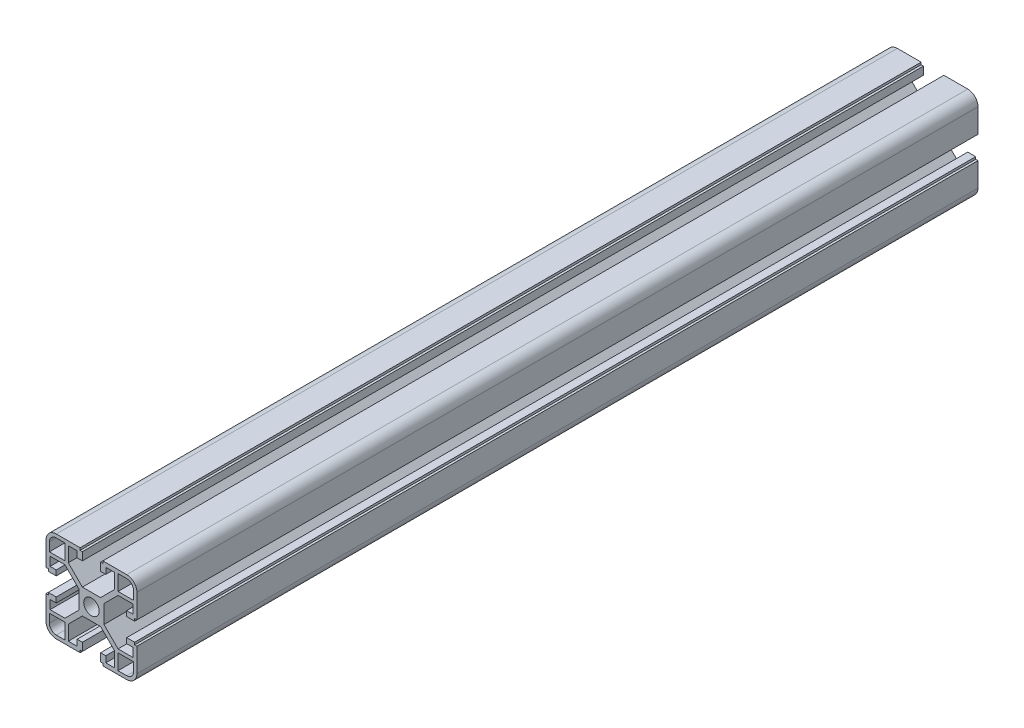
SolidWorks part; units mm, degrees
material "6061-T6 (SS)"
ref_plane "Front Plane" through (0, 0, 0) normal (0, 0, 1) x (1, 0, 0)
ref_plane "Top Plane" through (0, 0, 0) normal (0, 1, 0) x (1, 0, 0)
ref_plane "Right Plane" through (0, 0, 0) normal (1, 0, 0) x (0, 0, -1)
sketch "Sketch1" plane through (0, 0, 0) normal (0, 0, 1) x (1, 0, 0)
  line L0 (3.4, 0) -> (5.5, 0)
  line L1 (10.19, 11.69) -> (4, 5.5)
  line L2 (11.69, 10.19) -> (5.5, 4)
  line L3 (18.2, 10.19) -> (11.69, 10.19)
  line L4 (18.2, 10.19) -> (18.2, 6.3)
  line L5 (18.2, 6.3) -> (15.5, 6.3)
  line L6 (15.5, 6.3) -> (15.5, 4)
  line L7 (15.5, 4) -> (19, 4)
  line L8 (19, 4) -> (19, 5)
  line L9 (19, 5) -> (20, 5)
  line L10 (20, 5) -> (20, 15.5)
  line L11 (15.5, 20) -> (5, 20)
  line L12 (18.5, 11.69) -> (18.5, 15.5)
  line L13 (15.5, 18.5) -> (11.69, 18.5)
  line L14 (11.69, 11.69) -> (11.69, 18.5)
  line L15 (0, 3.4) -> (0, 5.5)
  line L16 (4, 5.5) -> (0, 5.5)
  line L17 (5, 20) -> (5, 19)
  line L18 (5.5, 0) -> (5.5, 4)
  line L19 (5, 19) -> (4, 19)
  line L20 (4, 19) -> (4, 15.5)
  line L21 (4, 15.5) -> (6.3, 15.5)
  line L22 (10.19, 11.69) -> (10.19, 18.2)
  line L23 (11.69, 11.69) -> (18.5, 11.69)
  line L24 (6.3, 18.2) -> (6.3, 15.5)
  line L25 (10.19, 18.2) -> (6.3, 18.2)
  arc A0 (20, 15.5) -> (15.5, 20) centre (15.5, 15.5) ccw
  arc A1 (18.5, 15.5) -> (15.5, 18.5) centre (15.5, 15.5) ccw
  arc A2 (3.4, 0) -> (0, 3.4) centre (0, 0) ccw
  point P4 (0, 4.45)
  dimension "D3" = 4.5
  dimension "D18" = 1.5
  dimension "D9" = 3.4
  dimension "D20" = 1.8
  dimension "D25" = 3
  dimension "D1" = 5.5
  dimension "D2" = 1.5
  dimension "D4" = 14.5
  dimension "D5" = 1.5
  dimension "D6" = 2.1
  dimension "D7" = 2.3
  dimension "D8" = 1.8
  dimension "D10" = 6.81
  dimension "D11" = 2.1
  dimension "D12" = 1
  dimension "D13" = 4.5
  dimension "D14" = 45
  dimension "D15" = 14.5
  dimension "D16" = 1
  dimension "D17" = 1.5
  dimension "D19" = 6.81
  dimension "D21" = 4.5
  dimension "D22" = 2.3
  dimension "D23" = 1
  dimension "D24" = 1
  dimension "D26" = 8.754
  dimension "D27" = 8.754
  dimension "D28" = 4
  dimension "D29" = 4
extrude "Boss-Extrude1" add sketch "Sketch1" along normal blind 370
mirror "Mirror1" about plane through (0, 0, 0) normal (0, 1, 0) of "Boss-Extrude1"
mirror "Mirror2" about plane through (0, 0, 0) normal (1, 0, 0) of "Boss-Extrude1"
mirror "Mirror3" about plane through (0, 0, 0) normal (0, 1, 0) of "Mirror2"
